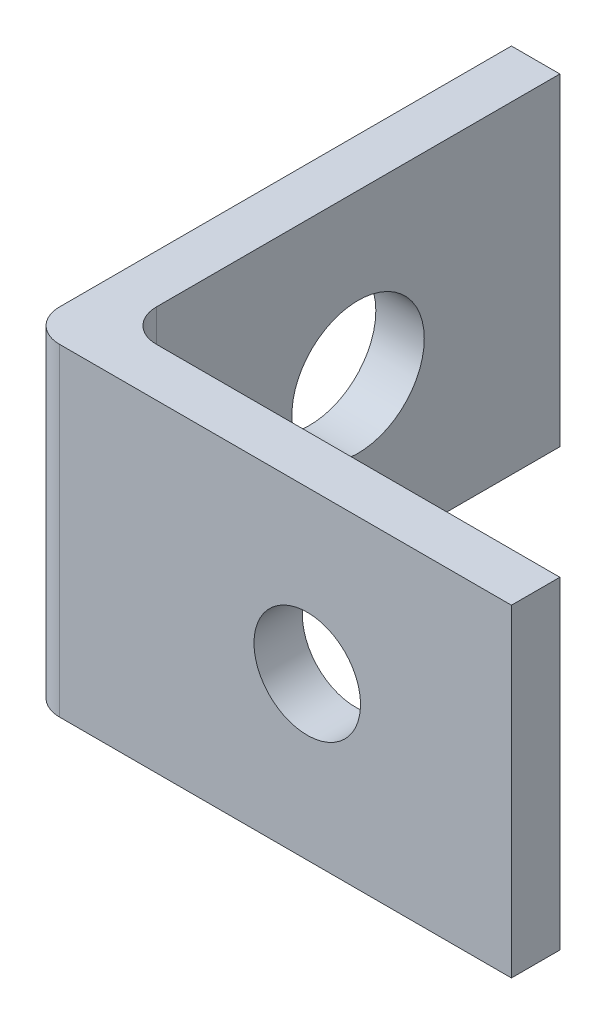
SolidWorks part; units mm, degrees
material "AISI 1020"
ref_plane "Спереди" through (0, 0, 0) normal (0, 0, 1) x (1, 0, 0)
ref_plane "Сверху" through (0, 0, 0) normal (0, 1, 0) x (1, 0, 0)
ref_plane "Справа" through (0, 0, 0) normal (1, 0, 0) x (0, 0, -1)
sketch "Эскиз1" plane through (0, 0, 0) normal (0, 1, 0) x (1, 0, 0)
  line L0 (0, 1) -> (0, 15)
  line L5 (0, 15) -> (1.5, 15)
  line L6 (1, 0) -> (15, 0)
  line L7 (15, 0) -> (15, 1.5)
  line L8 (15, 1.5) -> (2.5, 1.5)
  line L9 (1.5, 2.5) -> (1.5, 15)
  arc A0 (1, 0) -> (0, 1) centre (1, 1) cw
  arc A1 (2.5, 1.5) -> (1.5, 2.5) centre (2.5, 2.5) cw
  point P0 (0, 0)
  point P10 (0, 0)
  dimension "D5" = 1
  dimension "D1" = 15
  dimension "D2" = 1.5
  dimension "D3" = 15
  dimension "D4" = 1.5
extrude "Бобышка-Вытянуть1" add sketch "Эскиз1" along normal blind 10
sketch "Эскиз2" plane through (0, 0, 0) normal (0, 0, 1) x (1, 0, 0)
  line L0 (8.25, 0) -> (8.25, 11.3489) construction
  line L3 (1, 0) -> (15, 0) construction
  line L4 (15, 10) -> (15, 0) construction
  dimension "D1" = 6.75
sketch "Эскиз3" plane through (0, 0, 0) normal (-1, 0, 0) x (0, 0, 1)
  line L0 (-8.25, 0) -> (-8.25, 11.1434) construction
  line L1 (-15, 0) -> (-1, 0) construction
  dimension "D1" = 6.75
extrude "Вырез-Вытянуть3" cut sketch "Эскиз6" against normal blind 8 contours L4 A0 | A0 L4 region at (7.9754, 5.0104, -1.5) region at (9.3758, 4.9896, -1.5)
sketch "Эскиз6" plane through (-307.9408, -349.2045, -1.5) normal (0, 0, -1) x (-0.9999, 0.0149, 0)
  line L2 (-317.5586, 363.9713) -> (-305.06, 363.7853)
  line L3 (-317.7074, 353.9725) -> (-305.2088, 353.7864)
  line L4 (-311.3093, 363.8783) -> (-311.3093, 353.8772) construction
  circle A0 centre (-311.3093, 358.8778) radius 1.65
sketch "Эскиз12" plane through (1.5, 0, 0) normal (1, 0, 0) x (0, 0, -1)
  line L0 (8.75, 10) -> (8.75, 0) construction
  line L4 (2.5, 0) -> (15, 0)
  line L5 (15, 0) -> (15, 10)
  line L6 (15, 10) -> (2.5, 10)
  line L7 (2.5, 10) -> (2.5, 0)
  line L8 (2.5, 0) -> (15, 0) construction
  line L9 (15, 0) -> (15, 10) construction
  line L10 (15, 10) -> (2.5, 10) construction
  line L11 (2.5, 10) -> (2.5, 0) construction
  circle A0 centre (8.75, 5) radius 2.05
  dimension "D1" = 0
extrude "Вырез-Вытянуть5" cut sketch "Эскиз12" against normal blind 95
